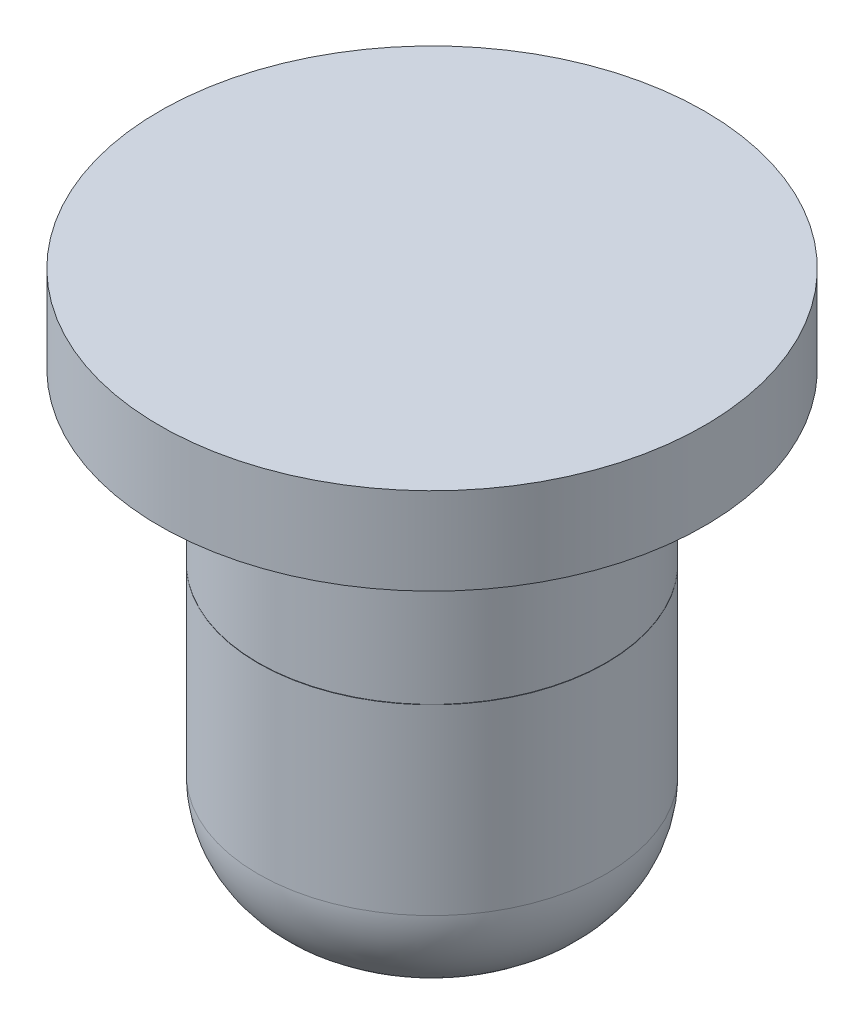
SolidWorks part; units mm, degrees
ref_plane "Front Plane" through (0, 0, 0) normal (0, 0, 1) x (1, 0, 0)
ref_plane "Top Plane" through (0, 0, 0) normal (0, 1, 0) x (1, 0, 0)
ref_plane "Right Plane" through (0, 0, 0) normal (1, 0, 0) x (0, 0, -1)
sketch "Sketch1" plane through (0, 0, 0) normal (0, 0, 1) x (1, 0, 0)
  line L0 (0, 18.6267) -> (19.8967, 18.6267)
  line L1 (19.8967, 18.6267) -> (19.8967, 12.2767)
  line L2 (19.8967, 12.2767) -> (12.7, 12.2767)
  line L3 (12.7, 12.2767) -> (12.7, -13.335)
  line L4 (5.08, -20.955) -> (0, -20.955)
  line L5 (0, -20.955) -> (0, 18.6267)
  arc A0 (12.7, -13.335) -> (5.08, -20.955) centre (5.08, -13.335) cw
  point P9 (12.7, -20.955)
  dimension "D2" = 7.62
  dimension "D1" = 12.7
revolve "Revolve1" add sketch "Sketch1" angle 360 about L5
sketch "Sketch2" plane through (0, 0, 0) normal (0, 0, 1) x (1, 0, 0)
  line L1 (-36.4156, 0) -> (36.4156, 0)
  line L2 (-36.4156, 0) -> (-36.4156, 0.0254)
  line L3 (-36.4156, 0.0254) -> (36.4156, 0.0254)
  line L4 (36.4156, 0) -> (36.4156, 0.0254)
  dimension "D1" = 0.0254
extrude "Cut-Extrude1" cut sketch "Sketch2" against normal through all both and the other way through all
